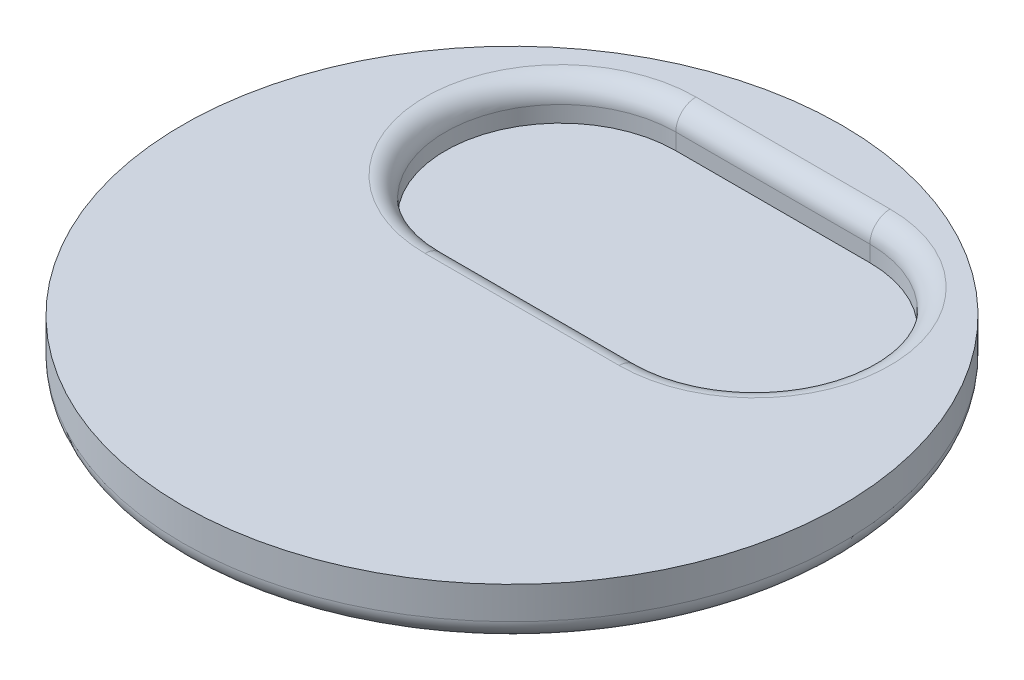
SolidWorks part; units mm, degrees
ref_plane "Front Plane" through (0, 0, 0) normal (0, 0, 1) x (1, 0, 0)
ref_plane "Top Plane" through (0, 0, 0) normal (0, 1, 0) x (1, 0, 0)
ref_plane "Right Plane" through (0, 0, 0) normal (1, 0, 0) x (0, 0, -1)
sketch "Sketch1" plane through (0, 0, 0) normal (0, 1, 0) x (1, 0, 0)
  line L0 (0, 0) -> (19.5381, 0) construction
  line L1 (0, 0) -> (-14.75, 0) construction
  line L2 (-2.4, 6.45) -> (2.4, 6.45)
  line L3 (-2.4, 0.75) -> (2.4, 0.75)
  line L4 (-2.4, 0) -> (-2.4, 11.5627) construction
  line L5 (2.4, 0) -> (2.4, 10.6684) construction
  circle A0 centre (0, 0) radius 8.15
  circle A3 centre (-2.4, 3.6) radius 2.85
  circle A4 centre (2.4, 3.6) radius 2.85
  dimension "D1" = 16.3
  dimension "D2" = 5.7
  dimension "D7" = 5.7
  dimension "D3" = 2.4
  dimension "D4" = 4.8
  dimension "D5" = 3.6
extrude "Boss-Extrude1" add sketch "Sketch1" along normal blind 1.3 contours A0 A4 A3 region at (0, 0, 1.2219)
extrude "Boss-Extrude2" add sketch "Sketch1<4>" along normal blind 0.4 contours A4 L2 A3 | A4 A3 | A3 A4 | A4 A3 | A4 A3 L3 region at (-2.5904, 0, -3.6) region at (0, 0, -6.0787) region at (2.5904, 0, -3.6) region at (0, 0, -1.1213) region at (0, 0, -3.6)
sketch "Sketch1<4>" plane through (0, 0, 0) normal (0, 1, 0) x (1, 0, 0) same geometry as "Sketch1"
fillet "Fillet3" radius 0.5 4 edges at (5.25, 1.3, -3.6) (-5.25, 1.3, -3.6) (0, 1.3, -6.45) (0, 1.3, -0.75)
fillet "Fillet4" radius 0.5 1 edges at (0, 0, 8.15)
